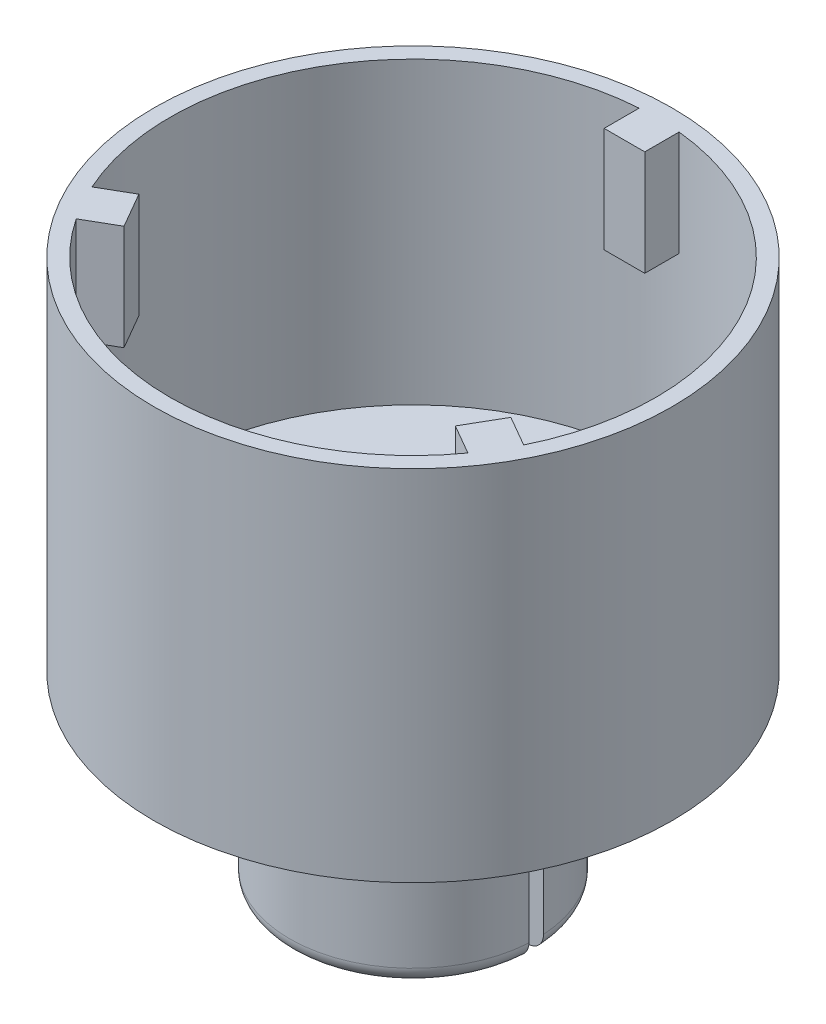
SolidWorks part; units mm, degrees
ref_plane "Front Plane" through (0, 0, 0) normal (0, 0, 1) x (1, 0, 0)
ref_plane "Top Plane" through (0, 0, 0) normal (0, 1, 0) x (1, 0, 0)
ref_plane "Right Plane" through (0, 0, 0) normal (1, 0, 0) x (0, 0, -1)
sketch "Sketch1" plane through (0, 0, 0) normal (0, 1, 0) x (1, 0, 0)
  circle A0 centre (0, 0) radius 32
  dimension "D1" = 64
extrude "Boss-Extrude1" add sketch "Sketch1" along normal blind 44.3
sketch "Sketch2" plane through (0, 44.3, 0) normal (0, 1, 0) x (1, 0, 0)
  circle A0 centre (0, 0) radius 30
  dimension "D1" = 60
extrude "Cut-Extrude1" cut sketch "Sketch2" against normal blind 37
sketch "Sketch3" plane through (0, 0, 0) normal (0, -1, 0) x (1, 0, 0)
  circle A0 centre (0, 0) radius 19.5
  dimension "D1" = 39
extrude "Boss-Extrude2" add sketch "Sketch3" along normal blind 7
sketch "Sketch4" plane through (0, -7, 0) normal (0, -1, 0) x (1, 0, 0)
  circle A0 centre (0, 0) radius 15.25
  dimension "D1" = 30.5
extrude "Boss-Extrude3" add sketch "Sketch4" along normal blind 16
fillet "Fillet1" radius 5 1 edges at (0, 0, -19.5)
sketch "Sketch5" plane through (0, 44.3, 0) normal (0, 1, 0) x (1, 0, 0)
  line L0 (-1.9905, 29.9339) -> (-1.9905, 25.6053)
  line L1 (-1.9905, 25.6053) -> (3.0302, 25.6053)
  line L2 (3.0302, 25.6053) -> (3.0302, 29.8466)
  line L3 (26.9188, -13.2431) -> (23.1701, -11.0788)
  line L4 (23.1701, -11.0788) -> (20.6597, -15.4269)
  line L5 (20.6597, -15.4269) -> (24.3328, -17.5475)
  line L6 (-24.9282, -16.6908) -> (-21.1796, -14.5265)
  line L7 (-21.1796, -14.5265) -> (-23.69, -10.1784)
  line L8 (-23.69, -10.1784) -> (-27.363, -12.299)
  circle A0 centre (0, 0) radius 30 construction
  arc A1 (24.3328, -17.5475) -> (26.9188, -13.2431) centre (0, 0) ccw
  circle A2 centre (0, 0) radius 30
  arc A3 (3.0302, 29.8466) -> (-1.9905, 29.9339) centre (0, 0) ccw
  arc A4 (-27.363, -12.299) -> (-24.9282, -16.6908) centre (0, 0) ccw
  point P19 (0, 0)
  dimension "D1" = 0
  dimension "D2" = 3
extrude "Boss-Extrude4" add sketch "Sketch5" against normal blind 13
sketch "Sketch7" plane through (0, -23, 0) normal (0, -1, 0) x (1, 0, 0)
  line L1 (33.0968, 0.9034) -> (-33.0968, 0.9034)
  line L2 (33.0968, 0.9034) -> (33.0968, -0.9034)
  line L3 (33.0968, -0.9034) -> (-33.0968, -0.9034)
  line L4 (-33.0968, 0.9034) -> (-33.0968, -0.9034)
  line L5 (33.0968, 0.9034) -> (-33.0968, -0.9034) construction
  line L6 (33.0968, -0.9034) -> (-33.0968, 0.9034) construction
  point P0 (0, 0)
extrude "Cut-Extrude2" cut sketch "Sketch7" against normal up to surface (16 mm away) up to face at (0, -7, -15.25)
fillet "Fillet2" radius 2 2 edges at (0, -23, 15.25) (0, -23, -15.25)
sketch "Sketch8" plane through (0, 7.3, 0) normal (0, 1, 0) x (1, 0, 0)
  circle A0 centre (0, 0) radius 10.3601
